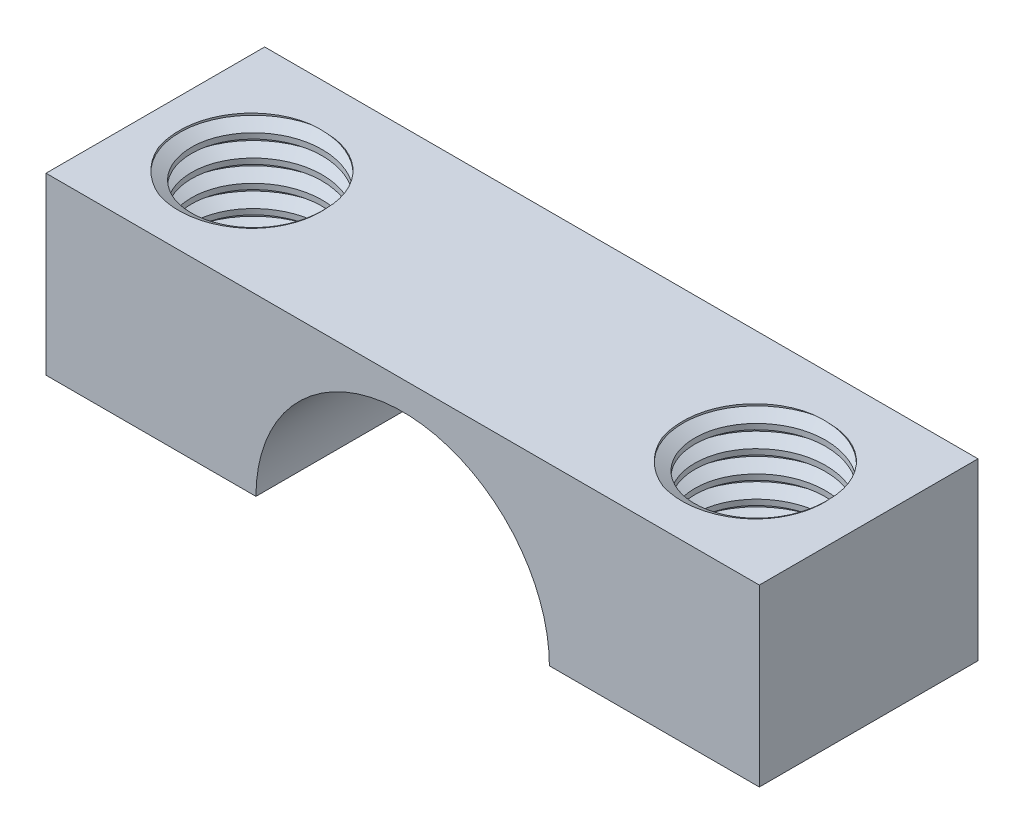
SolidWorks part; units mm, degrees
material "6061-T6 (SS)"
ref_plane "Front Plane" through (0, 0, 0) normal (0, 0, 1) x (1, 0, 0)
ref_plane "Top Plane" through (0, 0, 0) normal (0, 1, 0) x (1, 0, 0)
ref_plane "Right Plane" through (0, 0, 0) normal (1, 0, 0) x (0, 0, -1)
sketch "Sketch1" plane through (0, 0, 0) normal (0, 0, 1) x (1, 0, 0)
  line L1 (-8.155, -2) -> (8.155, -2)
  line L2 (-8.155, -2) -> (-8.155, 2)
  line L3 (-8.155, 2) -> (8.155, 2)
  line L4 (8.155, -2) -> (8.155, 2)
  line L5 (-8.155, -2) -> (8.155, 2) construction
  line L6 (-8.155, 2) -> (8.155, -2) construction
  point P0 (0, 0)
  dimension "D1" = 4
  dimension "D2" = 16.31
sketch "Sketch3" plane through (0, 0, 0) normal (0, 0, 1) x (1, 0, 0)
  line L0 (0, 0) -> (0, -2) construction
  line L1 (-8.155, -2) -> (8.155, -2) construction
  line L2 (-3.355, -2) -> (3.355, -2)
  line L3 (0, 1.355) -> (0, 2) construction
  line L4 (-8.155, 2) -> (8.155, 2) construction
  arc A0 (3.355, -2) -> (-3.355, -2) centre (0, -2) ccw
  point P8 (0, -2)
extrude "Boss-Extrude3" add sketch "Sketch1" against normal blind 5 contours L2 L3 L4 L1
extrude "Cut-Extrude9" cut sketch "Sketch3" against normal blind 5
sketch "Sketch4" plane through (0, 0, 0) normal (0, 1, 0) x (1, 0, 0)
  line L0 (0, 0) -> (0, 5) construction
  line L1 (-8.155, 0) -> (8.155, 0) construction
  line L2 (-8.155, 5) -> (8.155, 5) construction
  line L3 (0, 2.5) -> (5.755, 2.5) construction
  line L5 (0, 2.5) -> (-5.755, 2.5) construction
  circle A0 centre (-5.755, 2.5) radius 1.5
  circle A1 centre (5.755, 2.5) radius 1.5
extrude "Cut-Extrude10" cut sketch "Sketch4" against normal blind 2.5 and the other way blind 2.5 from offset 0
thread "Thread1" pitch 0.5 method cut profile "Thread Profile1" start angle 0, offset 0, length 5, pitch 0.5, diameter 3
ref_plane "Plane1" through (-4.255, -2, -2.5) normal (0, 0, 1) x (1, 0, 0)
sketch "Thread Profile1" plane through (-4.255, -2, -2.5) normal (0, 0, 1) x (1, 0, 0)
  line L0 (0, 0) -> (0, 0.5) construction
  line L1 (0, 0) -> (0.2706, 0.1562)
  line L2 (0.2706, 0.1562) -> (0.2706, 0.2187)
  line L3 (0.2706, 0.2187) -> (0, 0.375)
  line L4 (0.2706, 0.1875) -> (0, 0.1875) construction
  line L11 (0, 0) -> (0, 0.375)
  point P2 (0, 0)
  dimension "Pitch" = 0.5
  dimension "Profile_Angle" = 60
  dimension "Profile_Land" = 0.0625
  dimension "Profile_Height" = 0.2706
thread "Thread2" pitch 0.5 method cut profile "Thread Profile2" start angle 0, offset 0, length 5, pitch 0.5, diameter 3
ref_plane "Plane2" through (7.255, -2, -2.5) normal (0, 0, 1) x (1, 0, 0)
sketch "Thread Profile2" plane through (7.255, -2, -2.5) normal (0, 0, 1) x (1, 0, 0)
  line L0 (0, 0) -> (0, 0.5) construction
  line L1 (0, 0) -> (0.2706, 0.1562)
  line L2 (0.2706, 0.1562) -> (0.2706, 0.2187)
  line L3 (0.2706, 0.2187) -> (0, 0.375)
  line L4 (0.2706, 0.1875) -> (0, 0.1875) construction
  line L11 (0, 0) -> (0, 0.375)
  point P2 (0, 0)
  dimension "Pitch" = 0.5
  dimension "Profile_Angle" = 60
  dimension "Profile_Land" = 0.0625
  dimension "Profile_Height" = 0.2706
